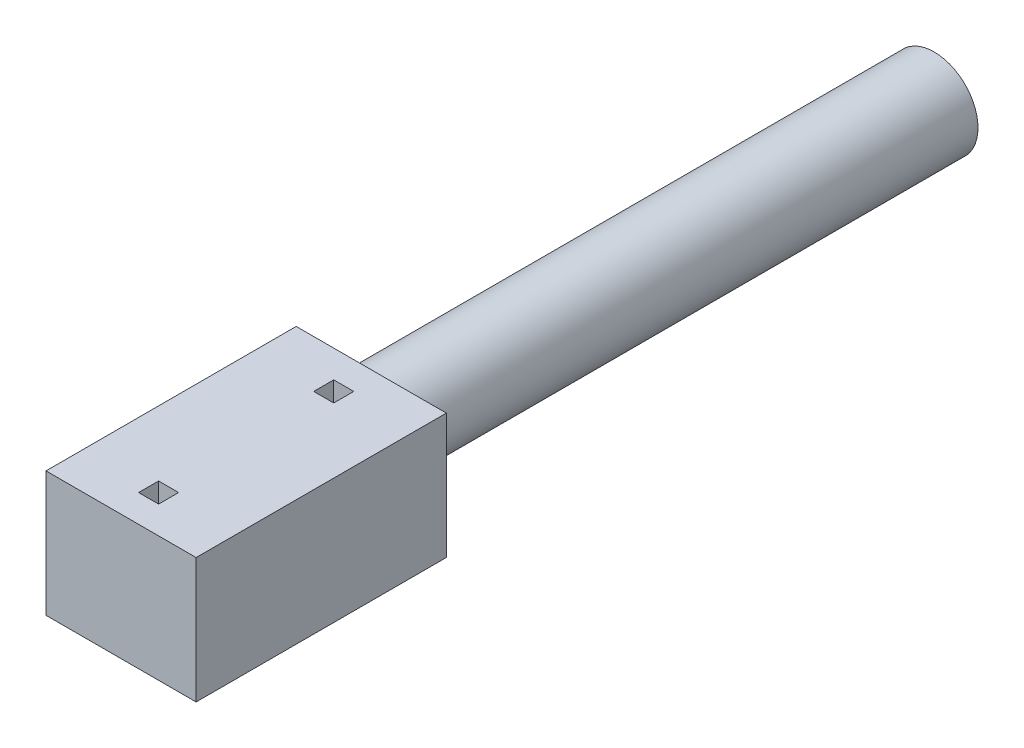
SolidWorks part; units mm, degrees
ref_plane "Front Plane" through (0, 0, 0) normal (0, 0, 1) x (1, 0, 0)
ref_plane "Top Plane" through (0, 0, 0) normal (0, 1, 0) x (1, 0, 0)
ref_plane "Right Plane" through (0, 0, 0) normal (1, 0, 0) x (0, 0, -1)
sketch "Sketch1" plane through (0, 0, 0) normal (0, 0, 1) x (1, 0, 0)
  line L1 (-6, 0) -> (6, 0)
  line L2 (-6, 0) -> (-6, 10)
  line L3 (-6, 10) -> (6, 10)
  line L4 (6, 0) -> (6, 10)
extrude "Boss-Extrude1" add sketch "Sketch1" along normal blind 20 from offset 10 offset against normal yes
sketch "Sketch2" plane through (0, 0, 0) normal (0, 0, 1) x (1, 0, 0)
  line L1 (-3.6, -1) -> (3.6, -1)
  line L2 (-3.6, -1) -> (-3.6, 4)
  line L3 (-3.6, 4) -> (3.6, 4)
  line L4 (3.6, -1) -> (3.6, 4)
extrude "Boss-Extrude2" add sketch "Sketch2" along normal blind 7.2 from offset 3.6 separate body offset against normal yes
combine bodies "Combine1" operation type subtract main body 101 bodies to subtract 102
sketch "Sketch3" plane through (0, 0, 0) normal (0, 0, 1) x (1, 0, 0)
  line L1 (-0.8, -1) -> (0.8, -1)
  line L2 (-0.8, -1) -> (-0.8, 11)
  line L3 (-0.8, 11) -> (0.8, 11)
  line L4 (0.8, -1) -> (0.8, 11)
extrude "Boss-Extrude3" add sketch "Sketch3" along normal blind 1.6 from offset 7.8 separate body offset against normal yes
combine bodies "Combine2" operation type subtract main body 103 bodies to subtract 104
sketch "Sketch4" plane through (0, 0, 0) normal (0, 0, 1) x (1, 0, 0)
  line L1 (-0.8, -1) -> (0.8, -1)
  line L2 (-0.8, -1) -> (-0.8, 11)
  line L3 (-0.8, 11) -> (0.8, 11)
  line L4 (0.8, -1) -> (0.8, 11)
extrude "Boss-Extrude4" add sketch "Sketch4" along normal blind 1.6 from offset 6.2 separate body
combine bodies "Combine3" operation type subtract main body 105 bodies to subtract 106
sketch "Sketch5" plane through (0, 0, 0) normal (0, 0, 1) x (1, 0, 0)
  circle A0 centre (0, 6) radius 3.5
extrude "Boss-Extrude5" add sketch "Sketch5" along normal blind 46 from offset 55 offset against normal yes
